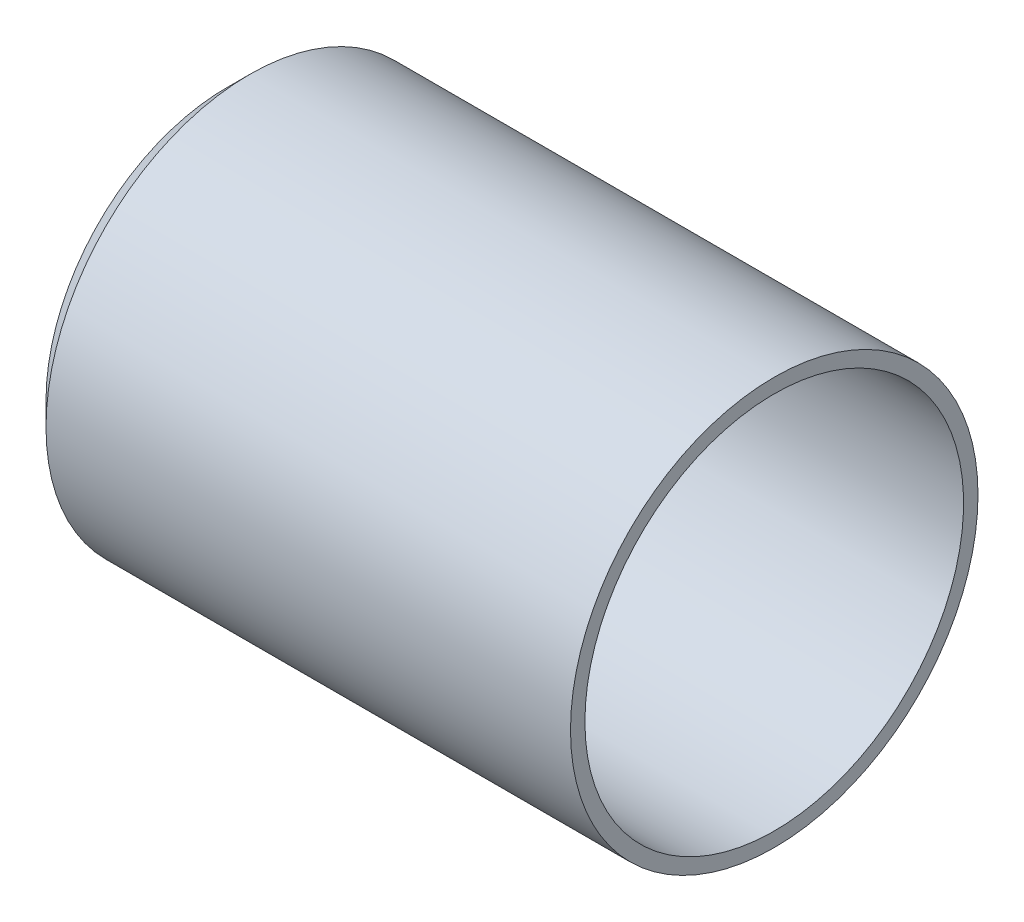
SolidWorks part; units mm, degrees
material "AISI 304"
ref_plane "Front Plane" through (0, 0, 0) normal (0, 0, 1) x (1, 0, 0)
ref_plane "Top Plane" through (0, 0, 0) normal (0, 1, 0) x (1, 0, 0)
ref_plane "Right Plane" through (0, 0, 0) normal (1, 0, 0) x (0, 0, -1)
sketch "Sketch1" plane through (0, 0, 0) normal (0, 0, 1) x (1, 0, 0)
  line L0 (0, 9.231) -> (0.5388, 8.6922)
  line L1 (0.5388, 8.6922) -> (1.524, 9.6774)
  line L2 (1.524, 9.6774) -> (27.9908, 9.6774)
  line L3 (27.9908, 9.6774) -> (27.9908, 10.414)
  line L4 (27.9908, 10.414) -> (1.183, 10.414)
  line L5 (1.183, 10.414) -> (0, 9.231)
  line L6 (27.9908, 0) -> (-27.9908, 0) construction
revolve "Revolve1" add sketch "Sketch1" angle 360 about L6 reverse direction yes
ref_plane "Plane1" through (1.524, 0, 0) normal (1, 0, 0) x (0, 0, -1)
ref_plane "Plane2" through (26.4668, 0, 0) normal (1, 0, 0) x (0, 0, -1)
ref_plane "Plane3" through (13.9954, 0, 0) normal (1, 0, 0) x (0, 0, -1)
ref_plane "Plane4" through (27.9908, 0, 0) normal (1, 0, 0) x (0, 0, -1)
ref_plane "body XY" through (27.9908, 0, 0) normal (1, 0, 0) x (0, 0, -1)
ref_plane "body XZ" through (0, 0, 0) normal (0, -1, 0) x (-1, 0, 0)
ref_plane "body YZ" through (0, 0, 0) normal (0, 0, -1) x (-1, 0, 0)
ref_axis "body X" through (27.9908, 0, 80.9) along (0, 0, -1)
ref_axis "body Y" through (27.9908, -50, 0) along (0, 1, 0)
ref_axis "body Z" through (80.9, 0, 0) along (-1, 0, 0)
sketch3d "body"
  point P0 (27.9908, 0, 0)
ref_plane "t1 XY" through (13.9954, 0, 0) normal (1, 0, 0) x (0, 0, -1)
ref_plane "t1 XZ" through (0, 10.414, 0) normal (0, -1, 0) x (-1, 0, 0)
ref_plane "t1 YZ" through (0, 0, 0) normal (0, 0, -1) x (-1, 0, 0)
ref_axis "t1 X" through (13.9954, 10.414, 80.9) along (0, 0, -1)
ref_axis "t1 Y" through (13.9954, -50, 0) along (0, 1, 0)
ref_axis "t1 Z" through (80.9, 10.414, 0) along (-1, 0, 0)
sketch3d "t1"
  point P0 (13.9954, 10.414, 0)
ref_plane "t2 XY" through (13.9954, 0, 0) normal (1, 0, 0) x (0, 0, -1)
ref_plane "t2 XZ" through (0, 0, 0) normal (0, -1, 0) x (-1, 0, 0)
ref_plane "t2 YZ" through (0, 0, -10.414) normal (0, 0, -1) x (-1, 0, 0)
ref_axis "t2 X" through (13.9954, 0, 80.9) along (0, 0, -1)
ref_axis "t2 Y" through (13.9954, -50, -10.414) along (0, 1, 0)
ref_axis "t2 Z" through (80.9, 0, -10.414) along (-1, 0, 0)
sketch3d "t2"
  point P0 (13.9954, 0, -10.414)
ref_plane "t3 XY" through (13.9954, 0, 0) normal (1, 0, 0) x (0, 0, -1)
ref_plane "t3 XZ" through (0, -10.414, 0) normal (0, -1, 0) x (-1, 0, 0)
ref_plane "t3 YZ" through (0, 0, 0) normal (0, 0, -1) x (-1, 0, 0)
ref_axis "t3 X" through (13.9954, -10.414, 80.9) along (0, 0, -1)
ref_axis "t3 Y" through (13.9954, -50, 0) along (0, 1, 0)
ref_axis "t3 Z" through (80.9, -10.414, 0) along (-1, 0, 0)
sketch3d "t3"
  point P0 (13.9954, -10.414, 0)
ref_plane "t4 XY" through (13.9954, 0, 0) normal (1, 0, 0) x (0, 0, -1)
ref_plane "t4 XZ" through (0, 0, 0) normal (0, -1, 0) x (-1, 0, 0)
ref_plane "t4 YZ" through (0, 0, 10.414) normal (0, 0, -1) x (-1, 0, 0)
ref_axis "t4 X" through (13.9954, 0, 80.9) along (0, 0, -1)
ref_axis "t4 Y" through (13.9954, -50, 10.414) along (0, 1, 0)
ref_axis "t4 Z" through (80.9, 0, 10.414) along (-1, 0, 0)
sketch3d "t4"
  point P0 (13.9954, 0, 10.414)
ref_plane "tube1 XY" through (1.524, 0, 0) normal (1, 0, 0) x (0, 0, -1)
ref_plane "tube1 XZ" through (0, 0, 0) normal (0, -1, 0) x (-1, 0, 0)
ref_plane "tube1 YZ" through (0, 0, 0) normal (0, 0, -1) x (-1, 0, 0)
ref_axis "tube1 X" through (1.524, 0, 80.9) along (0, 0, -1)
ref_axis "tube1 Y" through (1.524, -50, 0) along (0, 1, 0)
ref_axis "tube1 Z" through (80.9, 0, 0) along (-1, 0, 0)
sketch3d "tube1"
  point P0 (1.524, 0, 0)
ref_plane "tube2 XY" through (26.4668, 0, 0) normal (1, 0, 0) x (0, 0, -1)
ref_plane "tube2 XZ" through (0, 0, 0) normal (0, -1, 0) x (-1, 0, 0)
ref_plane "tube2 YZ" through (0, 0, 0) normal (0, 0, -1) x (-1, 0, 0)
ref_axis "tube2 X" through (26.4668, 0, 80.9) along (0, 0, -1)
ref_axis "tube2 Y" through (26.4668, -50, 0) along (0, 1, 0)
ref_axis "tube2 Z" through (80.9, 0, 0) along (-1, 0, 0)
sketch3d "tube2"
  point P0 (26.4668, 0, 0)
